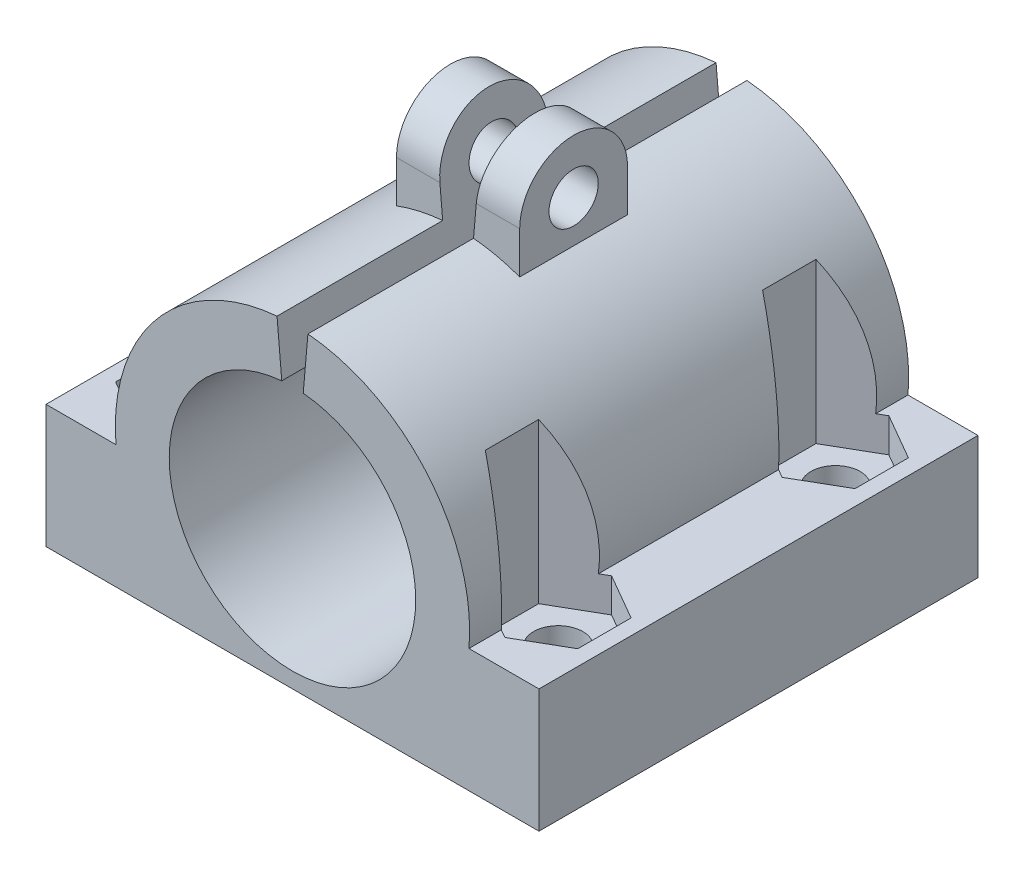
SolidWorks part; units mm, degrees
ref_plane "Front Plane" through (0, 0, 0) normal (0, 0, 1) x (1, 0, 0)
ref_plane "Top Plane" through (0, 0, 0) normal (0, 1, 0) x (1, 0, 0)
ref_plane "Right Plane" through (0, 0, 0) normal (1, 0, 0) x (0, 0, -1)
sketch "Sketch1" plane through (0, 0, 0) normal (0, 1, 0) x (1, 0, 0)
  line L1 (-16, 14.25) -> (16, 14.25)
  line L2 (-16, 14.25) -> (-16, -14.25)
  line L3 (-16, -14.25) -> (16, -14.25)
  line L4 (16, 14.25) -> (16, -14.25)
  line L5 (-16, 14.25) -> (16, -14.25) construction
  line L6 (-16, -14.25) -> (16, 14.25) construction
  point P0 (0, 0)
  dimension "D1" = 32
  dimension "D2" = 28.5
extrude "Boss-Extrude1" add sketch "Sketch1" along normal blind 8
sketch "Sketch3" plane through (0, 0, 14.25) normal (0, 0, 1) x (1, 0, 0)
  line L0 (0, 0) -> (0, 9) construction
  line L1 (-16, 0) -> (16, 0) construction
  line L2 (-7.1589, 0) -> (7.1589, 0)
  arc A0 (7.1589, 0) -> (-7.1589, 0) centre (0, 9) ccw
  dimension "D1" = 23
  dimension "D2" = 9
extrude "Boss-Extrude2" add sketch "Sketch3" against normal through all contours A0 L2
sketch "Sketch4" plane through (0, 0, 14.25) normal (0, 0, 1) x (1, 0, 0)
  line L0 (0, 20.5) -> (0, 0) construction
  line L1 (0, 9) -> (-11.5, 9) construction
  arc A0 (11.4564, 8) -> (-11.4564, 8) centre (0, 9) ccw construction
  circle A1 centre (0, 9) radius 8
  dimension "D1" = 16
  dimension "D2" = 0
extrude "Cut-Extrude2" cut sketch "Sketch4" against normal offset from surface (26.5 mm away) 2 up to face at (0, 7.4167, -14.25)
sketch "Sketch5" plane through (0, 0, -14.25) normal (0, 0, -1) x (-1, 0, 0)
  line L0 (0, 0) -> (0, 20.5) construction
  line L1 (8, 9) -> (-8, 9) construction
  arc A0 (11.4564, 8) -> (-11.4564, 8) centre (0, 9) ccw construction
  circle A1 centre (0, 9) radius 5
  circle A2 centre (0, 9) radius 8 construction
  circle A3 centre (0, 9) radius 8 construction
  dimension "D1" = 10
  dimension "D2" = 0
extrude "Cut-Extrude3" cut sketch "Sketch5" against normal through all
sketch "Sketch2" plane through (0, 8, 0) normal (0, 1, 0) x (1, 0, 0)
  line L0 (0, -14.25) -> (0, 14.25) construction
  line L1 (0, 0) -> (-16, 0) construction
  line L2 (-16, 14.25) -> (-16, -14.25) construction
  line L5 (-11.5, -14.25) -> (11.5, -14.25) construction
  line L6 (11.5, 14.25) -> (-11.5, 14.25) construction
  circle A0 centre (-12, 9) radius 1.6
  circle A1 centre (12, 9) radius 1.6
  circle A2 centre (12, -9) radius 1.6
  circle A3 centre (-12, -9) radius 1.6
  dimension "D3" = 3.2
  dimension "D1" = 12
  dimension "D2" = 9
extrude "Cut-Extrude1" cut sketch "Sketch2" against normal through all and the other way through all
sketch "Sketch6" plane through (0, 8, 0) normal (0, 1, 0) x (1, 0, 0)
  line L0 (-16, 0) -> (16, 0) construction
  line L1 (-16, 14.25) -> (-16, -14.25) construction
  line L2 (16, -14.25) -> (16, 14.25) construction
  line L3 (0, 14.25) -> (0, -14.25) construction
  line L4 (11.5, 14.25) -> (-11.5, 14.25) construction
  line L5 (-11.5, -14.25) -> (11.5, -14.25) construction
  line L6 (-12, 9) -> (-12, 12.4641) construction
  line L7 (-12, 12.4641) -> (-15, 10.7321)
  line L8 (-15, 10.7321) -> (-15, 7.2679)
  line L9 (-15, 7.2679) -> (-12, 5.5359)
  line L10 (-12, 5.5359) -> (-9, 7.2679)
  line L11 (-9, 7.2679) -> (-9, 10.7321)
  line L12 (-9, 10.7321) -> (-12, 12.4641)
  line L13 (-12, -9) -> (-12, -12.4641) construction
  line L14 (-9, -10.7321) -> (-12, -12.4641)
  line L15 (-9, -7.2679) -> (-9, -10.7321)
  line L16 (-12, -5.5359) -> (-9, -7.2679)
  line L17 (-15, -7.2679) -> (-12, -5.5359)
  line L18 (-15, -10.7321) -> (-15, -7.2679)
  line L19 (-12, -12.4641) -> (-15, -10.7321)
  line L20 (12, -9) -> (12, -12.4641) construction
  line L21 (12, 9) -> (12, 12.4641) construction
  line L22 (12, -12.4641) -> (15, -10.7321)
  line L23 (15, -10.7321) -> (15, -7.2679)
  line L24 (15, -7.2679) -> (12, -5.5359)
  line L25 (12, -5.5359) -> (9, -7.2679)
  line L26 (9, -7.2679) -> (9, -10.7321)
  line L27 (9, -10.7321) -> (12, -12.4641)
  line L28 (9, 10.7321) -> (12, 12.4641)
  line L29 (9, 7.2679) -> (9, 10.7321)
  line L30 (12, 5.5359) -> (9, 7.2679)
  line L31 (15, 7.2679) -> (12, 5.5359)
  line L32 (15, 10.7321) -> (15, 7.2679)
  line L33 (12, 12.4641) -> (15, 10.7321)
  circle A0 centre (-12, 9) radius 3 construction
  circle A1 centre (-12, -9) radius 3 construction
  circle A2 centre (12, -9) radius 3 construction
  circle A3 centre (12, 9) radius 3 construction
  circle A4 centre (-12, 9) radius 1.6 construction
  dimension "D2" = 0
  dimension "D1" = 6
extrude "Cut-Extrude4" cut sketch "Sketch6" along normal through all and the other way blind 2.2
sketch "Sketch8" plane through (0, 0, 0) normal (1, 0, 0) x (0, 0, -1)
  line L0 (0, 0) -> (0, 22.5) construction
  line L1 (-3.5, 22.5) -> (-3.5, 18.5)
  line L2 (-3.5, 18.5) -> (3.5, 18.5)
  line L3 (3.5, 18.5) -> (3.5, 22.5)
  line L4 (14.25, 20.5) -> (-14.25, 20.5) construction
  arc A0 (3.5, 22.5) -> (-3.5, 22.5) centre (0, 22.5) ccw
  circle A1 centre (0, 22.5) radius 1.6
  dimension "D1" = 7
  dimension "D4" = 3.2
  dimension "D2" = 2
  dimension "D3" = 4
extrude "Boss-Extrude3" add sketch "Sketch8" along normal blind 4 and the other way blind 4
sketch "Sketch9" plane through (0, 0, 14.25) normal (0, 0, 1) x (1, 0, 0)
  line L0 (0, 31) -> (0, 9) construction
  line L1 (0, 9) -> (1.7431, 28.9239)
  line L2 (0, 9) -> (-1.7431, 28.9239)
  arc A1 (1.7431, 28.9239) -> (-1.7431, 28.9239) centre (0, 9) ccw
  dimension "D2" = 40
  dimension "D1" = 5
extrude "Cut-Extrude5" cut sketch "Sketch9" against normal through all
equation "\"X-ROD-SPACING\"=45"
equation "\"Y-ROD-SPACING\"=75"
equation "\"Z-ROD-SPACING\"=17.5"
equation "\"Y-BED-OFFSET\"=2"
equation "\"Y-BED-ROD-INSET\"=3.5"
equation "\"T-SLOT-NUT-FILLET-RADIUS\"=0.25"
equation "\"T-SLOT-SCREW-SHAFT-RADIUS\"=1.75"
equation "\"T-SLOT-SCREW-SHAFT-CUTOUT-LENGTH\"=10.5"
equation "\"T-SLOT-NUT-DEPTH\"=4.2"
equation "\"T-SLOT-NUT-WIDTH\"=3"
equation "\"T-SLOT-NUT-END-DISTANCE\"=8"
equation "\"ACRYLIC-THICKNESS\"=10"
equation "\"ACRYLIC-THICKNESS2\"=4.5"
equation "\"ACRYLIC-TAB-CUTOUT-SIZE\"=\"ACRYLIC-THICKNESS\"+\"ACRYLIC-TAB-TOLERANCE\"*2"
equation "\"ACRYLIC-TAB-WIDTH\"=\"ACRYLIC-THICKNESS\""
equation "\"ACRYLIC-M3-HOLE\"=3.2"
equation "\"SMOOTHROD-CAP-SCREW-DISTANCE\"=20"
equation "\"FRAME-WIDTH-INNER\"=370"
equation "\"NEMA17-HOLE-SPACING\"=31"
equation "\"NEMA17-CENTRAL-CUTOUT\"=22.5"
equation "\"Z-BRACKET-REACH\"=55"
equation "\"TOP-BRACKET-SPACING\"=40"
equation "\"SMOOTHROD-X-LENGTH\"=350"
equation "\"SMOOTHROD-Y-LENGTH\"=350"
equation "\"SMOOTHROD-Z-LENGTH\"=350"
equation "\"SMOOTHROD-TIGHTENING-HEADROOM\"=1"
equation "\"LEADSCREW-Z-LENGTH\"=300"
equation "\"SCREW-LENGTH-FRAME\"=\"ACRYLIC-THICKNESS\" + 10"
equation "\"SCREW-HEAD-RADIUS\"=6"
equation "\"PRINTED-X-SMOOTHROD-DIAMETER\"=8.2"
equation "\"PRINTED-X-SMOOTHROD-CUTOUT\"=10"
equation "\"PRINTED-X-BASE-HEIGHT\"=10"
equation "\"PRINTED-LM8UU-CUTOUT-SIZE\"=16"
equation "\"PRINTED-LM8UU-CUTOUT-LENGTH\"=24.5"
equation "\"PRINTED-X-IDLER-HEIGHT\"=16"
equation "\"PSU-MOUNTING-WIDTH\"=95"
equation "\"PSU-MOUNTING-HEIGHT\"=177"
equation "\"Y-BELT-TO-ROD-DISTANCE\"=20"
equation "\"D3@Sketch2\"=3.2"
equation "\"D1@Sketch4\"=\"PRINTED-LM8UU-CUTOUT-SIZE\""
equation "\"D1@Sketch6\"=\"T-SLOT-NUT-WIDTH\"*2"
